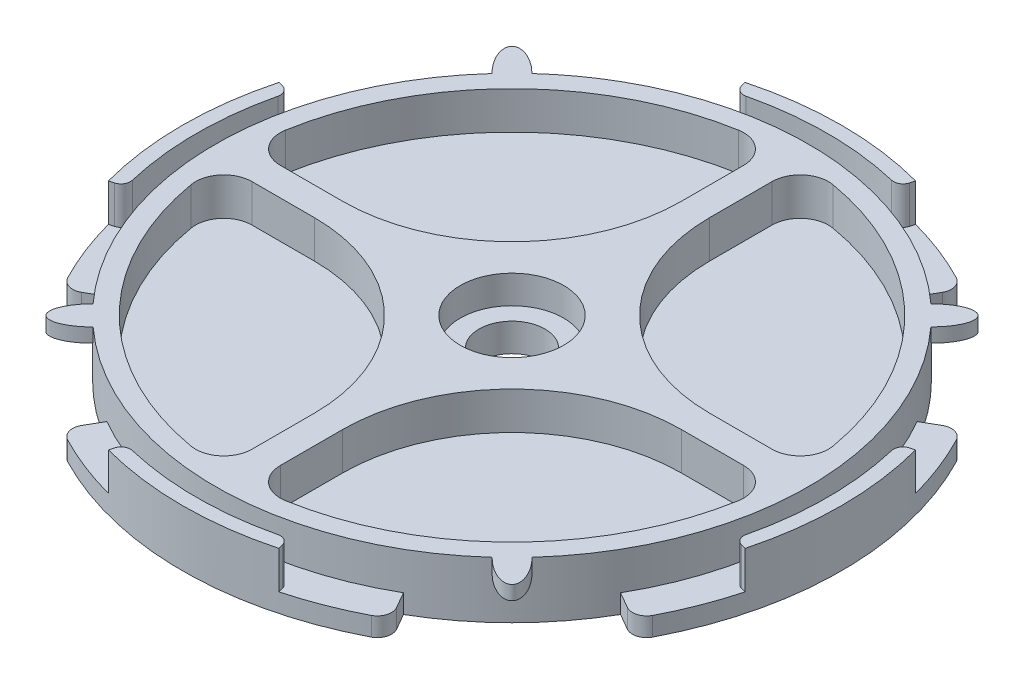
SolidWorks part; units mm, degrees
ref_plane "Front Plane" through (0, 0, 0) normal (0, 0, 1) x (1, 0, 0)
ref_plane "Top Plane" through (0, 0, 0) normal (0, 1, 0) x (1, 0, 0)
ref_plane "Right Plane" through (0, 0, 0) normal (1, 0, 0) x (0, 0, -1)
sketch "Sketch1" plane through (0, 0, 0) normal (0, 1, 0) x (1, 0, 0)
  circle A0 centre (0, 0) radius 35
  dimension "D1" = 70
extrude "Boss-Extrude1" add sketch "Sketch1" along normal blind 2
sketch "Sketch2" plane through (0, 2, 0) normal (0, 1, 0) x (1, 0, 0)
  circle A0 centre (0, 0) radius 31.5
  dimension "D1" = 63
extrude "Boss-Extrude2" add sketch "Sketch2" along normal blind 4
sketch "Sketch4" plane through (0, 2, 0) normal (0, 1, 0) x (1, 0, 0)
  circle A0 centre (0, 0) radius 35
  circle A1 centre (0, 0) radius 33.5
  circle A2 centre (0, 0) radius 35 construction
  dimension "D1" = 1.5
extrude "Boss-Extrude3" add sketch "Sketch4" along normal up to surface (4 mm away) up to face at (0, 6, 31.5)
sketch "Sketch5" plane through (0, 6, 0) normal (0, 1, 0) x (1, 0, 0)
  line L0 (0, 0) -> (35.9699, 35.9699) construction
  line L1 (0, 0) -> (60.1387, 0) construction
  line L2 (0, 0) -> (17.5, 30.3109) construction
  line L3 (0, 0) -> (30.3109, 17.5) construction
  line L4 (15.75, 27.2798) -> (17.5, 30.3109)
  line L5 (27.2798, 15.75) -> (30.3109, 17.5)
  arc A0 (27.2798, 15.75) -> (15.75, 27.2798) centre (0, 0) ccw
  circle A1 centre (0, 0) radius 31.5 construction
  arc A2 (30.3109, 17.5) -> (17.5, 30.3109) centre (0, 0) ccw
  circle A3 centre (0, 0) radius 35 construction
  dimension "D1" = 45
  dimension "D2" = 15
extrude "Cut-Extrude2" cut sketch "Sketch5" against normal through all
sketch "Sketch6" plane through (0, 6, 0) normal (0, 1, 0) x (1, 0, 0)
  line L0 (0, 0) -> (0, 44.9066) construction
  line L1 (0, 0) -> (49.8789, 0) construction
  line L2 (0, 0) -> (36.1286, 36.1286) construction
  line L3 (0, 0) -> (11.8027, 44.0484) construction
  line L4 (0, 0) -> (44.0484, 11.8027) construction
  line L5 (8.1528, 30.4267) -> (9.0587, 33.8074)
  line L6 (30.4267, 8.1528) -> (33.8074, 9.0587)
  arc A0 (33.8074, 9.0587) -> (9.0587, 33.8074) centre (0, 0) ccw
  arc A1 (30.4267, 8.1528) -> (8.1528, 30.4267) centre (0, 0) ccw
  arc A2 (15.75, 27.2798) -> (27.2798, 15.75) centre (0, 0) ccw construction
  arc A3 (17.5, 30.3109) -> (30.3109, 17.5) centre (0, 0) ccw construction
  dimension "D1" = 45
  dimension "D2" = 30
extrude "Cut-Extrude3" cut sketch "Sketch6" against normal up to surface (4 mm away) up to face at (-0.3915, 2, 0.3915)
sketch "Sketch7" plane through (0, 6, 0) normal (0, 1, 0) x (1, 0, 0)
  line L0 (0, 0) -> (0, 40.8739) construction
  line L1 (0, 0) -> (49.7748, 0) construction
  line L2 (0, 0) -> (33.072, 33.072) construction
  circle A0 centre (0, 0) radius 31.5 construction
  circle A1 centre (0, 0) radius 35 construction
  ellipse E0 centre (22.2739, 22.2739) end of major axis (24.7487, 24.7487) minor radius 1.5
  dimension "D1" = 45
  dimension "D2" = 3
extrude "Boss-Extrude4" add sketch "Sketch7" against normal blind 1.5
sketch "Sketch3" plane through (0, 6, 0) normal (0, 1, 0) x (1, 0, 0)
  line L0 (0, 0) -> (0, 37.6168) construction
  line L1 (0, 0) -> (43.5953, 0) construction
  line L2 (1.5, 1.5) -> (1.5, 29.4618)
  line L3 (1.5, 1.5) -> (29.4618, 1.5)
  arc A0 (29.4618, 1.5) -> (1.5, 29.4618) centre (0, 0) ccw
  circle A1 centre (0, 0) radius 31.5 construction
  dimension "D1" = 2
  dimension "D2" = 1.5
extrude "Cut-Extrude1" cut sketch "Sketch3" against normal up to surface (4 mm away) up to face at (10.892, 2, -10.892)
fillet "Fillet1" radius 18 1 edges at (1.5, 4, -1.5)
fillet "Fillet2" radius 3 2 edges at (29.4618, 4, -1.5) (1.5, 4, -29.4618)
fillet "Fillet3" radius 1.5 2 edges at (30.3109, 1, -17.5) (17.5, 1, -30.3109)
fillet "Fillet4" radius 1 2 edges at (8.6704, 4, -32.3585) (32.3585, 4, -8.6704)
pattern_circular "CirPattern1" count 4 over 360 about axis through (0, 6, 0) along (0, -1, 0) of "Cut-Extrude2", "Cut-Extrude3", "Boss-Extrude4", "Cut-Extrude1", "Fillet1", "Fillet2", "Fillet3", "Fillet4"
hole_wizard "CBORE for M6 Hex Socket Head Cap Screw1" positions "Sketch9" profile "Sketch8" counterbore size "M6" standard "ISO" end condition through all
sketch "Sketch9" plane through (0, 6, 0) normal (0, 1, 0) x (1, 0, 0)
  point P0 (0, 0)
sketch "Sketch8" plane through (0, 6, 0) normal (1, 0, 0) x (0, 0, 1)
  line L0 (0, 0) -> (0, 6)
  line L1 (0, 6) -> (3.5, 6)
  line L3 (3.5, 6) -> (3.5, 3)
  line L4 (3.5, 3) -> (5.5, 3)
  line L5 (5.5, 3) -> (5.5, 0)
  line L7 (5.5, 0) -> (0, 0)
  line L11 (0, -6.35) -> (0, 107.95) construction
  dimension "Thru Hole Dia." = 7
  dimension "Thru Hole Depth" = 6
  dimension "C'Bore Dia." = 11
  dimension "C'Bore Depth" = 3
